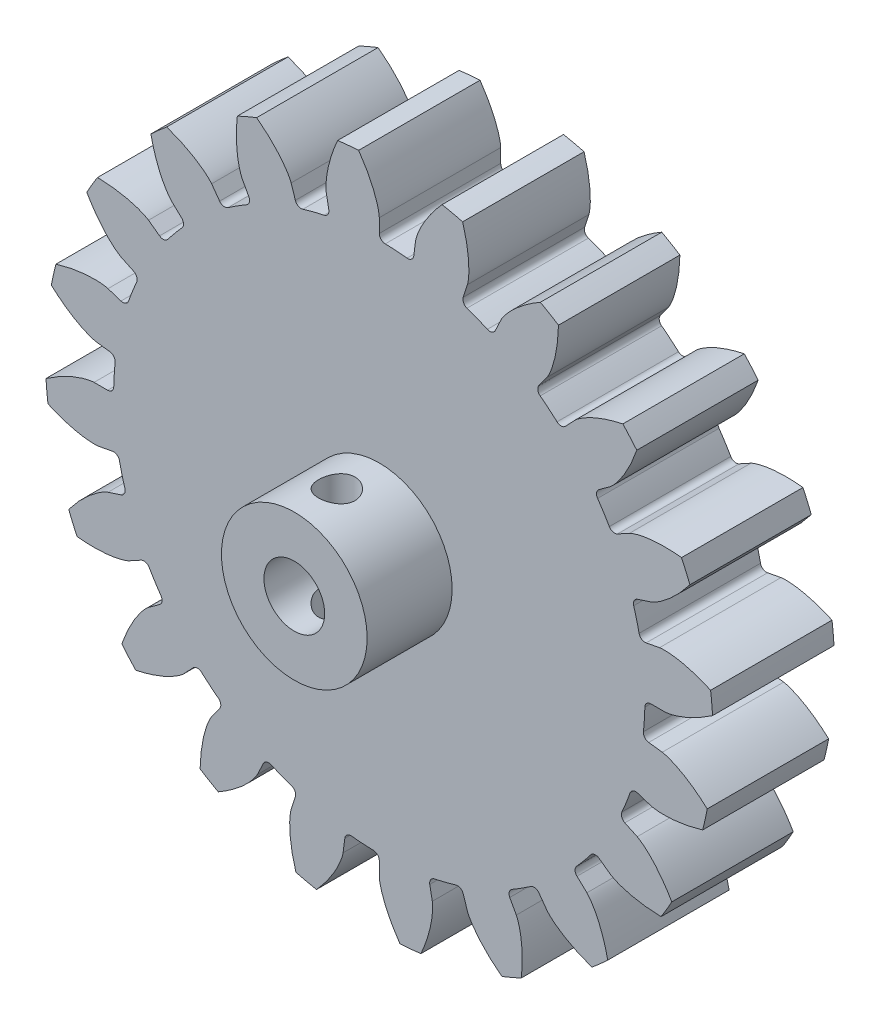
SolidWorks part; units mm, degrees
note: '?' marks a value the reader was unsure of.
material "Nylon 101"
ref_plane "Front Plane" through (0, 0, 0) normal (0, 0, 1) x (1, 0, 0)
ref_plane "Top Plane" through (0, 0, 0) normal (0, 1, 0) x (1, 0, 0)
ref_plane "Right Plane" through (0, 0, 0) normal (1, 0, 0) x (0, 0, -1)
sketch "Sketch1" plane through (0, 0, 0) normal (0, 0, 1) x (1, 0, 0)
  circle A0 centre (0, 0) radius 27.5
  dimension "D1" = 55
extrude "Boss-Extrude1" add sketch "Sketch1" along normal blind 10
sketch "Sketch2" plane through (0, 0, 10) normal (0, 0, 1) x (1, 0, 0)
  line L0 (22.3694, 0) -> (23.4923, 0)
  line L1 (0, 0) -> (27.4443, -1.7488) construction
  line L2 (22.1885, -2.8393) -> (23.3023, -2.9818)
  circle A0 centre (0, 0) radius 25 construction
  circle A1 centre (0, 0) radius 23.4923 construction
  arc A2 (21.7547, -2.291) -> (21.8695, -0.4888) centre (0, 0) ccw
  circle A3 centre (0, 0) radius 27.5 construction
  arc A4 (22.1885, -2.8393) -> (21.7547, -2.291) centre (22.252, -2.3433) cw
  arc A5 (21.8695, -0.4888) -> (22.3694, 0) centre (22.3694, -0.5) cw
  spline S0 degree 4 poles (23.4923, 0) (23.5003, 0.0001) (23.5229, 0.0008) (23.5654, 0.0035) (23.6347, 0.0099) (23.7229, 0.021) (23.8366, 0.0388) (23.9701, 0.064) (24.1163, 0.0963) (24.2747, 0.1362) (24.4321, 0.1804) (24.5885, 0.2284) (24.7436, 0.2799) (24.9307, 0.3464) (25.1538, 0.4321) (25.4127, 0.5406) (25.7039, 0.6737) (25.998, 0.82) (26.2849, 0.9725) (26.5718, 1.1365) (26.8473, 1.3021) (27.1301, 1.484) (27.3894, 1.6571) (27.6761, 1.8618) (27.9062, 2.0302) (28.2054, 2.2638) (28.3807, 2.4052) (28.5843, 2.5745) (28.6738, 2.6518) (28.729, 2.6993) knots 0 0 0 0 0 0.005377 0.015084 0.028532 0.04661 0.064855 0.092111 0.119476 0.146842 0.174209 0.201575 0.228941 0.256307 0.307035 0.361767 0.4165 0.471232 0.525964 0.580697 0.635429 0.690161 0.744894 0.799626 0.854358 0.909091 0.954545 1 1 1 1 1 construction
  spline S1 degree 4 poles (23.4923, 0) (23.5003, 0.0001) (23.5229, 0.0008) (23.5654, 0.0035) (23.6347, 0.0099) (23.7229, 0.021) (23.8366, 0.0388) (23.9701, 0.064) (24.1163, 0.0963) (24.2747, 0.1362) (24.4321, 0.1804) (24.5885, 0.2284) (24.7436, 0.2799) (24.9307, 0.3464) (25.1538, 0.4321) (25.4127, 0.5406) (25.7039, 0.6737) (25.998, 0.82) (26.2849, 0.9725) (26.5718, 1.1365) (26.8473, 1.3021) (27.1301, 1.484) (27.3894, 1.6571) (27.6761, 1.8618) (27.9062, 2.0302) (28.1405, 2.2132) (28.254, 2.3035) (28.3118, 2.3503) knots 0 0 0 0 0 0.005377 0.015084 0.028532 0.04661 0.064855 0.092111 0.119476 0.146842 0.174209 0.201575 0.228941 0.256307 0.307035 0.361767 0.4165 0.471232 0.525964 0.580697 0.635429 0.690161 0.744894 0.799626 0.854358 0.909091 0.909091 0.909091 0.909091 0.909091
  spline S2 degree 4 poles (23.3023, -2.9818) (23.3103, -2.983) (23.3325, -2.9865) (23.3744, -2.9946) (23.4423, -3.0097) (23.5284, -3.0319) (23.6389, -3.064) (23.7681, -3.106) (23.909, -3.1565) (24.0611, -3.2163) (24.2116, -3.2801) (24.3606, -3.3476) (24.5079, -3.4183) (24.6851, -3.508) (24.8955, -3.6213) (25.1385, -3.7618) (25.4105, -3.9308) (25.6836, -4.1132) (25.9489, -4.3009) (26.2126, -4.5) (26.4649, -4.6992) (26.7223, -4.9156) (26.9576, -5.1201) (27.2159, -5.3596) (27.4228, -5.5559) (27.6899, -5.8255) (27.8459, -5.988) (28.0263, -6.1818) (28.1053, -6.2699) (28.154, -6.324) knots 0 0 0 0 0 0.005377 0.015084 0.028532 0.04661 0.064855 0.092111 0.119476 0.146842 0.174209 0.201575 0.228941 0.256307 0.307035 0.361767 0.4165 0.471232 0.525964 0.580697 0.635429 0.690161 0.744894 0.799626 0.854358 0.909091 0.954545 1 1 1 1 1 construction
  spline S3 degree 4 poles (23.3023, -2.9818) (23.3103, -2.983) (23.3325, -2.9865) (23.3744, -2.9946) (23.4423, -3.0097) (23.5284, -3.0319) (23.6389, -3.064) (23.7681, -3.106) (23.909, -3.1565) (24.0611, -3.2163) (24.2116, -3.2801) (24.3606, -3.3476) (24.5079, -3.4183) (24.6851, -3.508) (24.8955, -3.6213) (25.1385, -3.7618) (25.4105, -3.9308) (25.6836, -4.1132) (25.9489, -4.3009) (26.2126, -4.5) (26.4649, -4.6992) (26.7223, -4.9156) (26.9576, -5.1201) (27.2159, -5.3596) (27.4228, -5.5559) (27.632, -5.7671) (27.7331, -5.8711) (27.7845, -5.9248) knots 0 0 0 0 0 0.005377 0.015084 0.028532 0.04661 0.064855 0.092111 0.119476 0.146842 0.174209 0.201575 0.228941 0.256307 0.307035 0.361767 0.4165 0.471232 0.525964 0.580697 0.635429 0.690161 0.744894 0.799626 0.854358 0.909091 0.909091 0.909091 0.909091 0.909091
  dimension "D1" = 50
  dimension "D2" = 46.9846
  dimension "D3" = 43.75
  dimension "D6" = 0.5
  dimension "D4" = 3.646
  dimension "D5" = 3.646
extrude "Cut-Extrude1" cut sketch "Sketch2" against normal through all and the other way through all
ref_axis "Axis2" through (0, 0, 10) along (0, 0, -1)?
pattern_circular "CirPattern6" count 20 over 360 about axis through (0, 0, 10) along (0, 0, -1) of "Cut-Extrude1"
sketch "Sketch3" plane through (0, 0, 10) normal (0, 0, 1) x (1, 0, 0)
  circle A0 centre (0, 0) radius 2.5
  circle A5 centre (0, 0) radius 7 construction
  dimension "D1" = 5
  dimension "D2" = 14
extrude "Cut-Extrude2" cut sketch "Sketch3" against normal blind 10
sketch "Sketch4" plane through (0, 0, 10) normal (0, 0, 1) x (1, 0, 0)
  circle A0 centre (0, 0) radius 2.5
  circle A1 centre (0, 0) radius 6
  dimension "D1" = 12
extrude "Boss-Extrude2" add sketch "Sketch4" along normal blind 7
ref_plane "Plane1" through (0, 0, 5) normal (0, 0, 1) x (1, 0, 0)
sketch "Sketch5" plane through (0, 0, 0) normal (0, 1, 0) x (1, 0, 0)
  line L0 (0, -10) -> (0, 0) construction
  line L1 (-23.4923, -10) -> (23.4923, -10) construction
  circle A0 centre (0, -13.5) radius 1.5
  dimension "D1" = 3
  dimension "D2" = 3.5
extrude "Cut-Extrude3" cut sketch "Sketch5" against normal through all and the other way through all
mirror "Mirror2" about plane through (0, 0, 5) normal (0, 0, 1) of "Boss-Extrude2", "Cut-Extrude3"
equation "\"m\"= 2.5'module"
equation "\"p\"= 1 / \"m\"'Diametral pitch"
equation "\"N\"= 20'Number of teeth"
equation "\"phi\"= 20'pressure angle"
equation "\"a\"= \"m\"'addendum"
equation "\"b\"= 1.25 * \"m\"'deddendum"
equation "\"c\"= \"b\" - \"a\"'clearance"
equation "\"dp\"= \"N\" * \"m\"'pitch circle diameter"
equation "\"db\"= \"dp\" * cos ( \"phi\" )'base circle diameter"
equation "\"D1@Sketch1\" = \"dp\" + 2 * \"a\"'Addendum circle dia "
equation "\"D1@Sketch2\" = \"dp\"'pitch circle dia "
equation "\"D2@Sketch2\"= \"db\" 'base circle dia"
equation "\"D3@Sketch2\"= \"dp\" - 2 * \"b\" 'deddendum circle dia"
equation "\"alpha\"= sqr ( \"dp\" ^ 2 - \"db\" ^ 2 ) / \"db\" * 180 / pi - \"phi\""
equation "\"D4@Sketch2\" = 360 / ( 4 * \"N\" ) - \"alpha\""
equation "\"D5@Sketch2\" = \"D4@Sketch2\""
equation "\"D6@Sketch2\" = 0.8 * \"c\""
